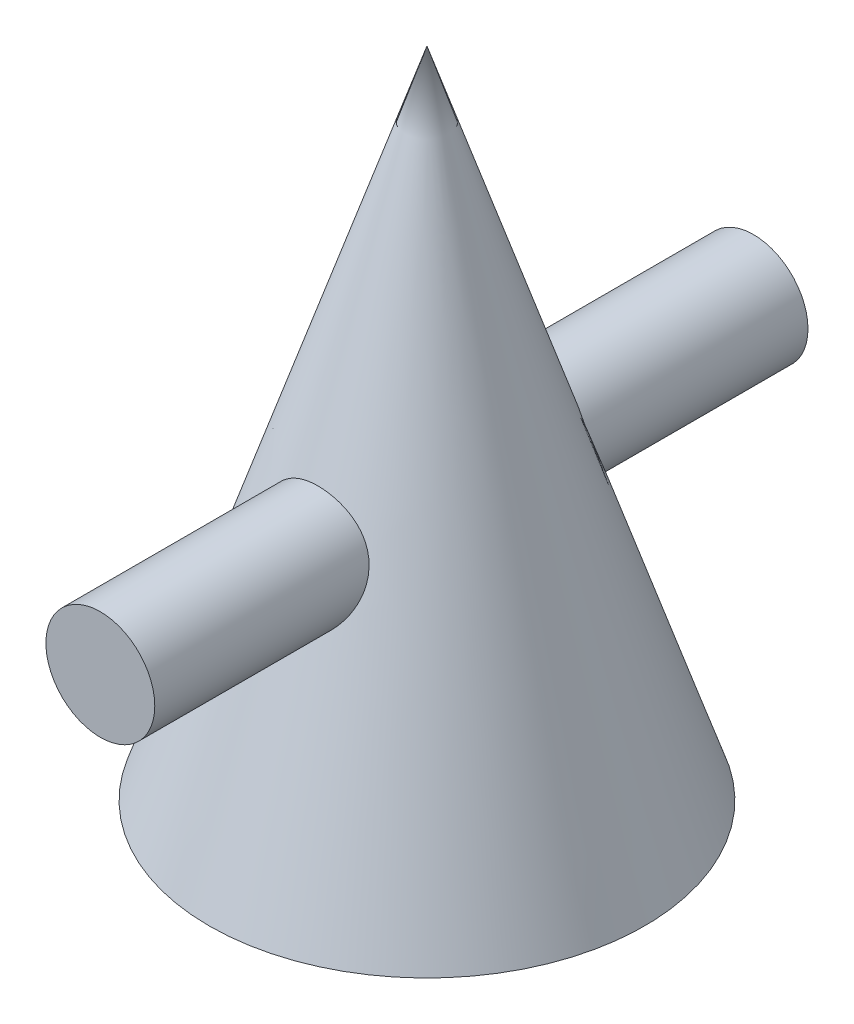
SolidWorks part; units mm, degrees
ref_plane "前视基准面" through (0, 0, 0) normal (0, 0, 1) x (1, 0, 0)
ref_plane "上视基准面" through (0, 0, 0) normal (0, 1, 0) x (1, 0, 0)
ref_plane "右视基准面" through (0, 0, 0) normal (1, 0, 0) x (0, 0, -1)
other "Configuration Table"
sketch "草图1" plane through (0, 0, 0) normal (0, 1, 0) x (1, 0, 0)
  circle A0 centre (0, 0) radius 20
sketch "草图2" plane through (0, 0, 0) normal (0, 0, 1) x (1, 0, 0)
  point P4 (0, 60)
loft "放样1" add profiles "草图2", "草图1"
sketch "草图3" plane through (0, 0, 0) normal (0, 0, 1) x (1, 0, 0)
  circle A0 centre (0, 25) radius 5
extrude "凸台-拉伸1" add sketch "草图3" along normal blind 30 and the other way blind 30
